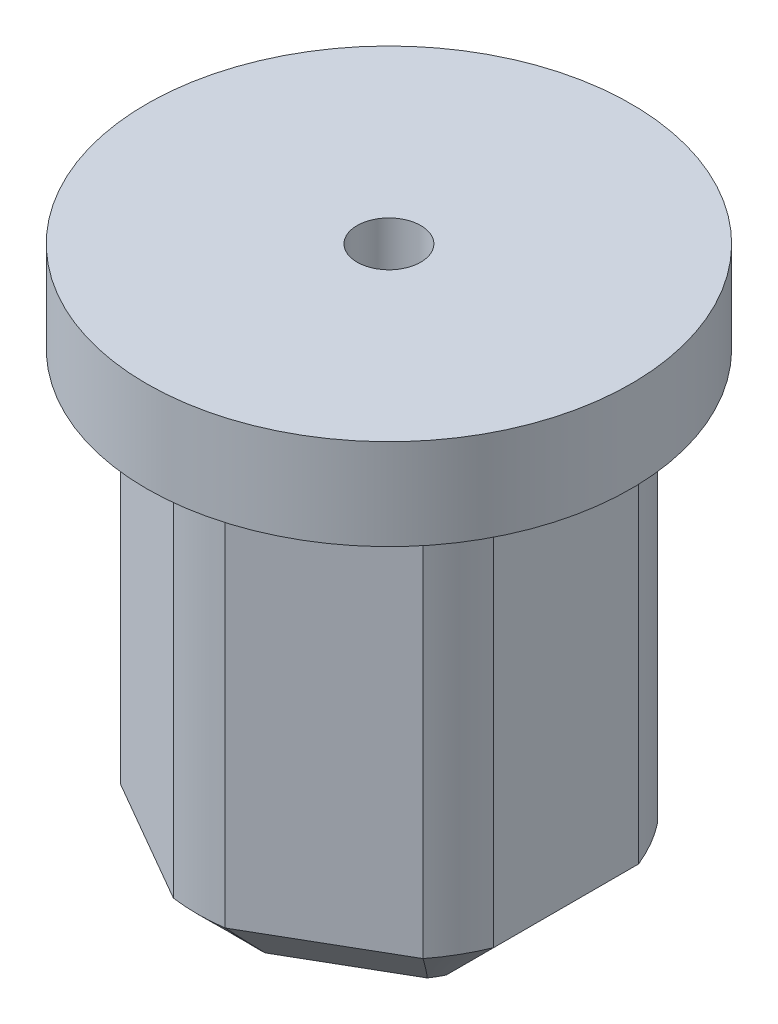
SolidWorks part; units mm, degrees
ref_plane "Front Plane" through (0, 0, 0) normal (0, 0, 1) x (1, 0, 0)
ref_plane "Top Plane" through (0, 0, 0) normal (0, 1, 0) x (1, 0, 0)
ref_plane "Right Plane" through (0, 0, 0) normal (1, 0, 0) x (0, 0, -1)
sketch "Sketch1" plane through (0, 0, 0) normal (0, 1, 0) x (1, 0, 0)
  circle A0 centre (0, 0) radius 8
  dimension "D1" = 16
extrude "Boss-Extrude1" add sketch "Sketch1" along normal blind 3
ref_axis "Axis1" through (0, 13.8986, 0) along (0, -1, 0)
sketch "Sketch9" plane through (0, 0, 0) normal (0, -1, 0) x (1, 0, 0)
  line L1 (0, -6.755) -> (5.85, -3.3775)
  line L2 (5.85, -3.3775) -> (5.85, 3.3775)
  line L3 (5.85, 3.3775) -> (0, 6.755)
  line L4 (0, 6.755) -> (-5.85, 3.3775)
  line L5 (-5.85, 3.3775) -> (-5.85, -3.3775)
  line L6 (-5.85, -3.3775) -> (0, -6.755)
  circle A0 centre (0, 0) radius 6.32
  circle A1 centre (0, 0) radius 5.85 construction
  dimension "D1" = 12.64
  dimension "D2" = 11.7
extrude "Boss-Extrude2" add sketch "Sketch9" along normal blind 15 contours L1 A0 L2 L3 L4 L5 L6 region at (0, 0, 0)
chamfer "Chamfer1" distance 2 angle 45 12 edges at (0, -15, -6.32) (-2.925, -15, -5.0662) (-5.4733, -15, -3.16) (-5.85, -15, 0) (-5.4733, -15, 3.16) (-2.925, -15, 5.0662) (0, -15, 6.32) (2.925, -15, 5.0662) (5.4733, -15, 3.16) (5.85, -15, 0) (5.4733, -15, -3.16) (2.925, -15, -5.0662)
sketch "Sketch10" plane through (0, -15, 0) normal (0, -1, 0) x (1, 0, 0)
  circle A0 centre (0, 0) radius 2.5
  dimension "D1" = 5
extrude "Cut-Extrude1" cut sketch "Sketch10" against normal up to surface (15 mm away) up to face at (0, 0, 8)
sketch "Sketch11" plane through (0, 3, 0) normal (0, 1, 0) x (1, 0, 0)
  circle A0 centre (0, 0) radius 1.984 construction
  circle A1 centre (0, 0) radius 1.984
  circle A2 centre (0, 0) radius 1.05
  dimension "D1" = 2.1
extrude "Cut-Extrude3" cut sketch "Sketch11" against normal through all contours A2 region at (0, 3, 0)
